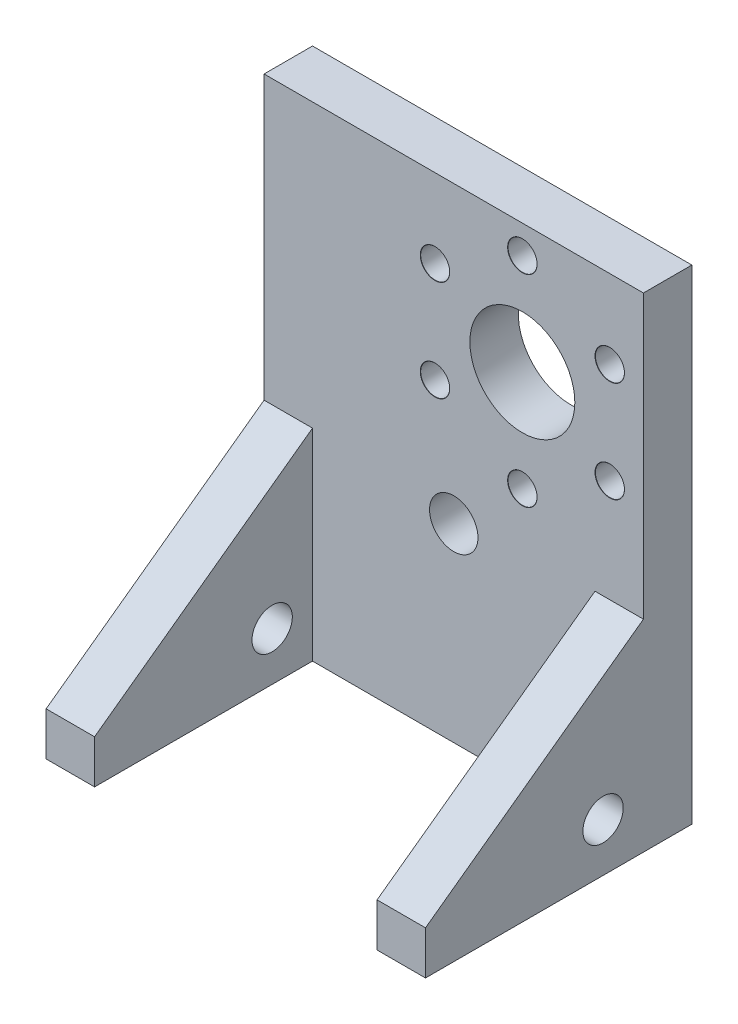
SolidWorks part; units mm, degrees
material "PLA"
ref_plane "Front Plane" through (0, 0, 0) normal (0, 0, 1) x (1, 0, 0)
ref_plane "Top Plane" through (0, 0, 0) normal (0, 1, 0) x (1, 0, 0)
ref_plane "Right Plane" through (0, 0, 0) normal (1, 0, 0) x (0, 0, -1)
sketch "Sketch1" plane through (0, 0, 0) normal (0, 1, 0) x (1, 0, 0)
  line L0 (-17.5, 0) -> (17.5, 0)
  line L1 (17.5, 0) -> (17.5, -27)
  line L2 (17.5, -27) -> (23.5, -27)
  line L3 (23.5, -27) -> (23.5, 6)
  line L4 (23.5, 6) -> (-23.5, 6)
  line L5 (-23.5, 6) -> (-23.5, -27)
  line L6 (-23.5, -27) -> (-17.5, -27)
  line L7 (-17.5, -27) -> (-17.5, 0)
  line L8 (-17.5, 0) -> (-23.5, 0)
  line L9 (17.5, 0) -> (23.5, 0)
  line L10 (-20.5, -15) -> (-20.5, 3) construction
  line L11 (-20.5, 3) -> (20.5, 3) construction
  line L12 (20.5, 3) -> (20.5, -15) construction
  point P8 (0, 0)
  point P12 (-20.5, -15)
  point P13 (20.5, -15)
  point P14 (20.5, 3)
  point P15 (-20.5, 3)
  dimension "D1" = 6
  dimension "D2" = 6
  dimension "D3" = 6
  dimension "D4" = 35
  dimension "D5" = 27
  dimension "D6" = 18
extrude "Boss-Extrude1" add sketch "Sketch1" along normal blind 5 contours L7 L8 L5 L6 | L0 L9 L3 L4 L5 L8 | L9 L1 L2 L3 region at (0, 0, -3) region at (-20.5, 0, 13.5) region at (20.5, 0, 13.5)
extrude "Boss-Extrude2" add sketch "Sketch1<3>" along normal blind 55 from surface contours L0 L9 L3 L4 L5 L8 region at (0, 0, -3) starting at face at (0, 5, 12)
sketch "Sketch1<3>" plane through (0, 0, 0) normal (0, 1, 0) x (1, 0, 0) same geometry as "Sketch1"
ref_plane "Plane1" through (-23.5, 5, 0) normal (-1, 0, 0) x (0, 0, 1)
chamfer "Chamfer1" distance 20 angle 54 2 edges at (20.5, 5, 0) (-20.5, 5, 0) first distance on face at (0, 17.5, 0)
sketch "Sketch4" plane through (0, 0, 0) normal (0, 0, 1) x (1, 0, 0)
  line L1 (-17.5, 0) -> (17.5, 0) construction
  line L2 (23.5, 60) -> (23.5, 25) construction
  circle A0 centre (8.5, 44) radius 12.5 construction
  circle A1 centre (8.5, 44) radius 6.5
  point P0 (8.5, 44)
  point P7 (8.5, 56.5)
  point P11 (19.3253, 50.25)
  point P12 (19.3253, 37.75)
  point P13 (8.5, 31.5)
  point P14 (-2.3253, 37.75)
  point P15 (-2.3253, 50.25)
  point P16 (8.5, 44)
  dimension "D3" = 25
  dimension "D5" = 13
  dimension "D1" = 15
  dimension "D2" = 44
  dimension "D4" = 6
hole_wizard "M3 Clearance Hole1" positions "Sketch5" profile "Sketch6" hole size "M3" standard "ISO" end condition through all
sketch "Sketch5" plane through (0, 0, 0) normal (0, 0, 1) x (1, 0, 0)
  point P0 (8.5, 56.5)
  point P3 (19.3253, 50.25)
  point P6 (19.3253, 37.75)
  point P9 (8.5, 31.5)
  point P12 (-2.3253, 37.75)
  point P15 (-2.3253, 50.25)
sketch "Sketch6" plane through (8.5, 56.5, 0) normal (1, 0, 0) x (0, -1, 0)
  line L0 (0, 0) -> (0, 6)
  line L1 (0, 6) -> (1.8, 6)
  line L2 (1.8, 6) -> (1.8, 0.025)
  line L3 (1.8, 0.025) -> (1.825, 0)
  line L5 (1.825, 0) -> (0, 0)
  line L6 (-1.8, 0.025) -> (-1.825, 0) construction
  line L11 (0, -6.35) -> (0, 107.95) construction
  dimension "Thru Hole Dia." = 3.6
  dimension "Thru Hole Depth" = 6
  dimension "Near C'Sink Dia." = 3.65
  dimension "Near C'Sink Angle" = 90
extrude "Cut-Extrude1" cut sketch "Sketch4" against normal through all both and the other way through all
hole_wizard "Ø5.3 (5.3) Diameter Hole1" positions "Sketch7" profile "Sketch9" hole size "Ø5.3" standard "ISO"
sketch "Sketch7" plane through (0, 0, 0) normal (0, -1, 0) x (-1, 0, 0)
  point P0 (-20.5, 3)
  point P3 (-20.5, -15)
  point P6 (20.5, 3)
  point P9 (20.5, -15)
sketch "Sketch9" plane through (20.5, 0, -3) normal (1, 0, 0) x (0, 0, -1)
  line L0 (0, 0) -> (0, 8.5923)
  line L1 (0, 8.5923) -> (2.65, 7)
  line L2 (2.65, 7) -> (2.65, 0)
  line L5 (2.65, 0) -> (0, 0)
  line L10 (0, 8.5923) -> (-2.65, 7) construction
  line L11 (0, -6.35) -> (0, 107.95) construction
  dimension "Hole Dia." = 5.3
  dimension "Hole Depth" = 7
  dimension "Drill Angle" = 118
sketch "Sketch10" plane through (0, 0, 0) normal (0, 0, 1) x (1, 0, 0)
  line L0 (-17.5, 0) -> (17.5, 0) construction
  circle A0 centre (0, 23.5) radius 3
  dimension "D2" = 6
  dimension "D1" = 23.5
extrude "Cut-Extrude2" cut sketch "Sketch10" against normal blind 10
sketch "Sketch11" plane through (-23.5, 0, 0) normal (-1, 0, 0) x (0, 0, 1)
  line L0 (-6, 0) -> (27, 0) construction
  line L1 (0, 60) -> (0, 25) construction
  circle A0 centre (5, 6) radius 2.5
  dimension "D1" = 5
  dimension "D2" = 6
  dimension "D3" = 5
extrude "Cut-Extrude3" cut sketch "Sketch11" against normal through all
